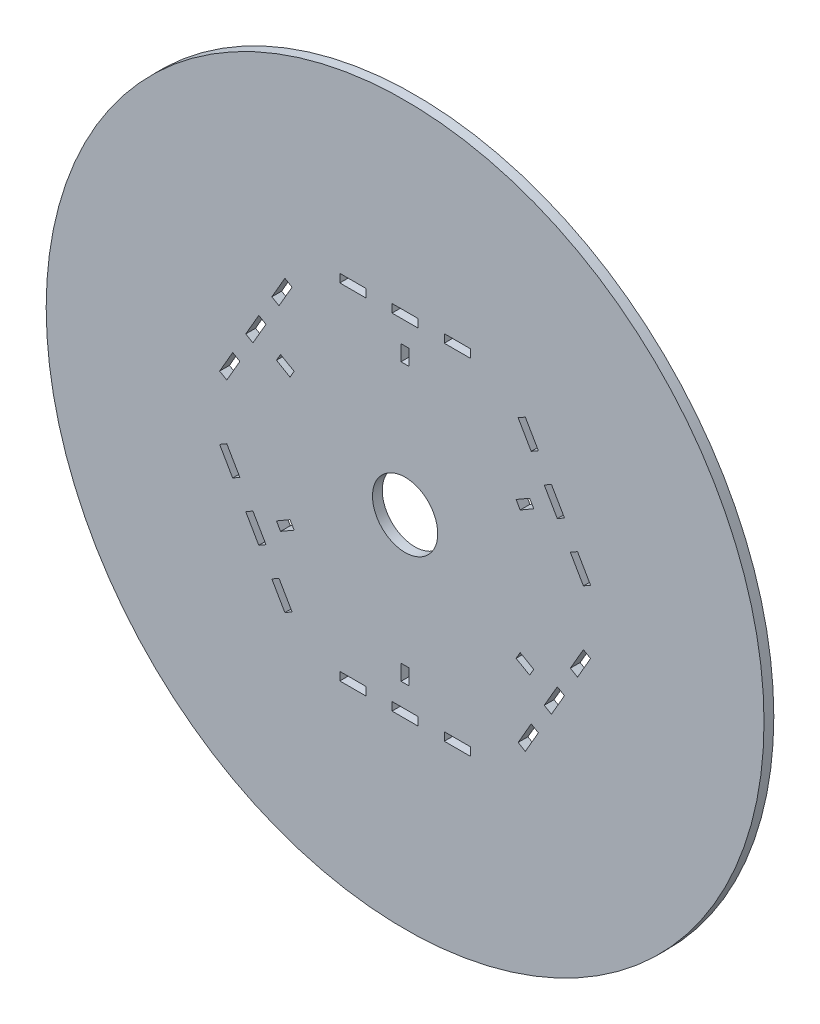
SolidWorks part; units mm, degrees
ref_plane "Front Plane" through (0, 0, 0) normal (0, 0, 1) x (1, 0, 0)
ref_plane "Top Plane" through (0, 0, 0) normal (0, 1, 0) x (1, 0, 0)
ref_plane "Right Plane" through (0, 0, 0) normal (1, 0, 0) x (0, 0, -1)
sketch "Sketch1" plane through (0, 0, 0) normal (0, 0, 1) x (1, 0, 0)
  line L0 (5, 67.6125) -> (-5, 67.6125)
  line L1 (-5, 67.6125) -> (-5, 64.4375)
  line L2 (-5, 64.4375) -> (5, 64.4375)
  line L3 (-15, 67.6125) -> (-5, 67.6125) construction
  line L4 (-15, 67.6125) -> (-25, 67.6125)
  line L5 (-15, 67.6125) -> (-15, 64.4375)
  line L6 (-15, 64.4375) -> (-25, 64.4375)
  line L7 (-25, 67.6125) -> (-25, 64.4375)
  line L8 (25, 67.6125) -> (25, 64.4375)
  line L9 (15, 64.4375) -> (25, 64.4375)
  line L10 (15, 67.6125) -> (15, 64.4375)
  line L11 (15, 67.6125) -> (25, 67.6125)
  line L12 (15, 67.6125) -> (5, 67.6125) construction
  line L13 (5, 67.6125) -> (5, 64.4375)
  line L14 (1.5625, 56) -> (-1.5625, 56)
  line L15 (-1.5625, 56) -> (-1.5625, 50)
  line L16 (-1.5625, 50) -> (1.5625, 50)
  line L17 (1.5625, 56) -> (1.5625, 50)
  line L18 (0, 64.4375) -> (0, 56) construction
  line L19 (0, 50) -> (0, 0) construction
  line L20 (61.0541, 29.4761) -> (56.0541, 38.1364)
  line L21 (56.0541, 38.1364) -> (53.3045, 36.5489)
  line L22 (53.3045, 36.5489) -> (58.3045, 27.8886)
  line L23 (51.0541, 46.7966) -> (46.0541, 55.4569)
  line L24 (51.0541, 46.7966) -> (48.3045, 45.2091)
  line L25 (48.3045, 45.2091) -> (43.3045, 53.8694)
  line L26 (46.0541, 55.4569) -> (43.3045, 53.8694)
  line L27 (71.0541, 12.1556) -> (68.3045, 10.5681)
  line L28 (63.3045, 19.2284) -> (68.3045, 10.5681)
  line L29 (66.0541, 20.8159) -> (63.3045, 19.2284)
  line L30 (66.0541, 20.8159) -> (71.0541, 12.1556)
  line L31 (61.0541, 29.4761) -> (58.3045, 27.8886)
  line L32 (49.2787, 26.6468) -> (47.7162, 29.3532)
  line L33 (47.7162, 29.3532) -> (42.52, 26.3532)
  line L34 (42.52, 26.3532) -> (44.0825, 23.6468)
  line L35 (49.2787, 26.6468) -> (44.0825, 23.6468)
  line L36 (51.0541, 46.7966) -> (56.0541, 38.1364) construction
  line L37 (66.0541, 20.8159) -> (61.0541, 29.4761) construction
  line L38 (55.8045, 32.2188) -> (48.4974, 28) construction
  line L39 (56.0541, -38.1364) -> (61.0541, -29.4761)
  line L40 (61.0541, -29.4761) -> (58.3045, -27.8886)
  line L41 (58.3045, -27.8886) -> (53.3045, -36.5489)
  line L42 (66.0541, -20.8159) -> (71.0541, -12.1556)
  line L43 (66.0541, -20.8159) -> (63.3045, -19.2284)
  line L44 (63.3045, -19.2284) -> (68.3045, -10.5681)
  line L45 (71.0541, -12.1556) -> (68.3045, -10.5681)
  line L46 (46.0541, -55.4569) -> (43.3045, -53.8694)
  line L47 (48.3045, -45.2091) -> (43.3045, -53.8694)
  line L48 (51.0541, -46.7966) -> (48.3045, -45.2091)
  line L49 (51.0541, -46.7966) -> (46.0541, -55.4569)
  line L50 (56.0541, -38.1364) -> (53.3045, -36.5489)
  line L51 (47.7162, -29.3532) -> (49.2787, -26.6468)
  line L52 (49.2787, -26.6468) -> (44.0825, -23.6468)
  line L53 (44.0825, -23.6468) -> (42.52, -26.3532)
  line L54 (47.7162, -29.3532) -> (42.52, -26.3532)
  line L55 (66.0541, -20.8159) -> (61.0541, -29.4761) construction
  line L56 (51.0541, -46.7966) -> (56.0541, -38.1364) construction
  line L57 (55.8045, -32.2187) -> (48.4974, -28) construction
  line L58 (-5, -67.6125) -> (5, -67.6125)
  line L59 (5, -67.6125) -> (5, -64.4375)
  line L60 (5, -64.4375) -> (-5, -64.4375)
  line L61 (15, -67.6125) -> (25, -67.6125)
  line L62 (15, -67.6125) -> (15, -64.4375)
  line L63 (15, -64.4375) -> (25, -64.4375)
  line L64 (25, -67.6125) -> (25, -64.4375)
  line L65 (-25, -67.6125) -> (-25, -64.4375)
  line L66 (-15, -64.4375) -> (-25, -64.4375)
  line L67 (-15, -67.6125) -> (-15, -64.4375)
  line L68 (-15, -67.6125) -> (-25, -67.6125)
  line L69 (-5, -67.6125) -> (-5, -64.4375)
  line L70 (-1.5625, -56) -> (1.5625, -56)
  line L71 (1.5625, -56) -> (1.5625, -50)
  line L72 (1.5625, -50) -> (-1.5625, -50)
  line L73 (-1.5625, -56) -> (-1.5625, -50)
  line L74 (15, -67.6125) -> (5, -67.6125) construction
  line L75 (-15, -67.6125) -> (-5, -67.6125) construction
  line L76 (0, -64.4375) -> (0, -56) construction
  line L77 (-61.0541, -29.4761) -> (-56.0541, -38.1364)
  line L78 (-56.0541, -38.1364) -> (-53.3045, -36.5489)
  line L79 (-53.3045, -36.5489) -> (-58.3045, -27.8886)
  line L80 (-51.0541, -46.7966) -> (-46.0541, -55.4569)
  line L81 (-51.0541, -46.7966) -> (-48.3045, -45.2091)
  line L82 (-48.3045, -45.2091) -> (-43.3045, -53.8694)
  line L83 (-46.0541, -55.4569) -> (-43.3045, -53.8694)
  line L84 (-71.0541, -12.1556) -> (-68.3045, -10.5681)
  line L85 (-63.3045, -19.2284) -> (-68.3045, -10.5681)
  line L86 (-66.0541, -20.8159) -> (-63.3045, -19.2284)
  line L87 (-66.0541, -20.8159) -> (-71.0541, -12.1556)
  line L88 (-61.0541, -29.4761) -> (-58.3045, -27.8886)
  line L89 (-49.2787, -26.6468) -> (-47.7162, -29.3532)
  line L90 (-47.7162, -29.3532) -> (-42.52, -26.3532)
  line L91 (-42.52, -26.3532) -> (-44.0825, -23.6468)
  line L92 (-49.2787, -26.6468) -> (-44.0825, -23.6468)
  line L93 (-51.0541, -46.7966) -> (-56.0541, -38.1364) construction
  line L94 (-66.0541, -20.8159) -> (-61.0541, -29.4761) construction
  line L95 (-55.8045, -32.2188) -> (-48.4974, -28) construction
  line L96 (-56.0541, 38.1364) -> (-61.0541, 29.4761)
  line L97 (-61.0541, 29.4761) -> (-58.3045, 27.8886)
  line L98 (-58.3045, 27.8886) -> (-53.3045, 36.5489)
  line L99 (-66.0541, 20.8159) -> (-71.0541, 12.1556)
  line L100 (-66.0541, 20.8159) -> (-63.3045, 19.2284)
  line L101 (-63.3045, 19.2284) -> (-68.3045, 10.5681)
  line L102 (-71.0541, 12.1556) -> (-68.3045, 10.5681)
  line L103 (-46.0541, 55.4569) -> (-43.3045, 53.8694)
  line L104 (-48.3045, 45.2091) -> (-43.3045, 53.8694)
  line L105 (-51.0541, 46.7966) -> (-48.3045, 45.2091)
  line L106 (-51.0541, 46.7966) -> (-46.0541, 55.4569)
  line L107 (-56.0541, 38.1364) -> (-53.3045, 36.5489)
  line L108 (-47.7162, 29.3532) -> (-49.2787, 26.6468)
  line L109 (-49.2787, 26.6468) -> (-44.0825, 23.6468)
  line L110 (-44.0825, 23.6468) -> (-42.52, 26.3532)
  line L111 (-47.7162, 29.3532) -> (-42.52, 26.3532)
  line L112 (-66.0541, 20.8159) -> (-61.0541, 29.4761) construction
  line L113 (-51.0541, 46.7966) -> (-56.0541, 38.1364) construction
  line L114 (-55.8045, 32.2188) -> (-48.4974, 28) construction
  circle A0 centre (0, 0) radius 137.5
  circle A1 centre (0, 0) radius 12.5
  point P3 (0, 67.6125)
  point P13 (0, 64.4375)
  point P18 (0, 50)
  point P19 (0, 56)
  point P31 (58.5541, 33.8062)
  point P41 (55.8045, 32.2188)
  point P46 (43.3013, 25)
  point P47 (48.4974, 28)
  point P53 (58.5541, -33.8063)
  point P63 (55.8045, -32.2187)
  point P68 (43.3013, -25)
  point P69 (48.4974, -28)
  point P75 (0, -67.6125)
  point P85 (0, -64.4375)
  point P90 (0, -50)
  point P91 (0, -56)
  point P97 (-58.5541, -33.8063)
  point P107 (-55.8045, -32.2188)
  point P112 (-43.3013, -25)
  point P113 (-48.4974, -28)
  point P119 (-58.5541, 33.8063)
  point P129 (-55.8045, 32.2188)
  point P134 (-43.3013, 25)
  point P135 (-48.4974, 28)
  point P138 (0, 0)
  dimension "D8" = 275
  dimension "D9" = 25
  dimension "D1" = 3.175
  dimension "D2" = 10
  dimension "D3" = 1.5625
  dimension "D4" = 6
  dimension "D5" = 8.4375
  dimension "D6" = 50
  dimension "D7" = 6
extrude "Boss-Extrude1" add sketch "Sketch1" along normal mid plane 3.75
